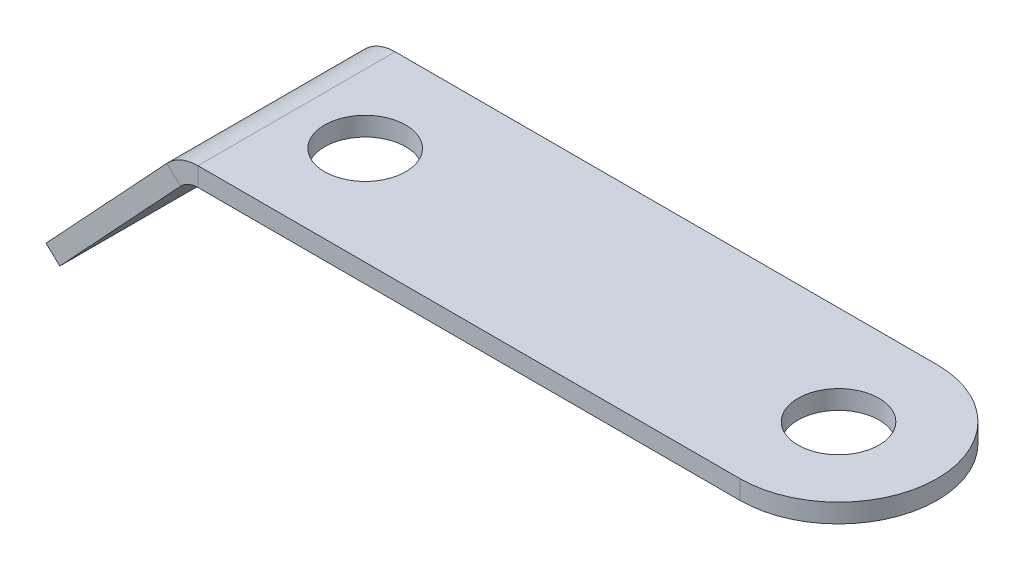
SolidWorks part; units mm, degrees
note: The reader was unsure of these and kept them because the rebuilt part matched: flange length of "Edge-Flange1".
ref_plane "Front Plane" through (0, 0, 0) normal (0, 0, 1) x (1, 0, 0)
ref_plane "Top Plane" through (0, 0, 0) normal (0, 1, 0) x (1, 0, 0)
ref_plane "Right Plane" through (0, 0, 0) normal (1, 0, 0) x (0, 0, -1)
sketch "Sketch1" plane through (0, 0, 0) normal (0, 1, 0) x (1, 0, 0)
  line L0 (44.45, 0) -> (44.45, 4.6736) construction
  line L1 (0, 0) -> (44.45, 0)
  line L2 (0, 0) -> (0, 15.875)
  line L3 (0, 15.875) -> (44.45, 15.875)
  line L4 (44.45, 11.2014) -> (44.45, 15.875) construction
  line L5 (44.45, 4.6736) -> (44.45, 11.2014) construction
  arc A0 (44.45, 15.875) -> (44.45, 0) centre (44.45, 7.9375) cw
  circle A1 centre (44.45, 7.9375) radius 3.2639
  circle A2 centre (6.35, 7.9375) radius 3.2639
  dimension "D3" = 6.5278
  dimension "D4" = 6.5278
  dimension "D1" = 15.875
  dimension "D2" = 44.45
  dimension "D5" = 38.1
base flange "Base-Flange1" sketch "Sketch1" thickness 1.5189 reverse thickness direction no parameters "D1"=1.905
edge flange "Edge-Flange1" sketch "Sketch8" flange angle 133 flange length 15.748 flange position material outside bend radius 1.905 thickness 1.5189 relief rectangular parameters "D6"=10
sketch "Sketch8" plane through (0, -1.5189, 0) normal (-0.7314, 0.682, 0) x (0, 0, -1)
  line L2 (0, 0) -> (0, 15.0876)
  line L3 (0, 15.0876) -> (15.875, 15.0876)
  line L4 (15.875, 15.0876) -> (15.875, 0)
  line L11 (15.875, 0) -> (0, 0) construction
  line L12 (15.875, 0) -> (0, 0)
bend "EdgeBend1" bend radius 1.905 bend angle 47 parameters "D5"=1
sketch "Bend-Lines1" [suppressed] plane through (0, 0, 0) normal (0, 1, 0) x (1, 0, 0)
sketch "Bounding-Box1" [suppressed] plane through (0, 0, 0) normal (0, 1, 0) x (1, 0, 0)
sheet metal parameters "Sheet-Metal1" thickness 1.5189 parameters "D1"=1.905
flat pattern "Flat-Pattern1" [suppressed]
sketch "Bend-Lines2" plane through (0, 0, 0) normal (0, 1, 0) x (1, 0, 0)
sketch3d "Bounding-Box2" [suppressed]
  line L0 (44.45, 7.9375, 0) -> (-7.9374, 7.9375, 0) construction
  line L1 (44.45, -7.9375, 0) -> (-7.9374, -7.9375, 0) construction
  line L2 (44.45, 7.9375, 0) -> (44.45, -7.9375, 0) construction
  line L3 (-7.9374, 7.9375, 0) -> (-7.9374, -7.9375, 0) construction
sheet metal parameters "Sheet-Metal2" thickness 1.5189 parameters "D1"=1.905
flat pattern "Flat-Pattern1"
sketch "Bend-Lines2" plane through (0, 0, 0) normal (0, 1, 0) x (1, 0, 0)
  line L0 (-0.2645, 15.875) -> (-0.2645, 0) construction
  line L1 (-0.2645, 15.875) -> (-0.2645, 0) construction
sketch3d "Bounding-Box2" [suppressed]
  line L0 (-60.0666, 7.9375, 0) -> (7.9374, 7.9375, 0) construction
  line L1 (-60.0666, -7.9375, 0) -> (7.9374, -7.9375, 0) construction
  line L2 (-60.0666, 7.9375, 0) -> (-60.0666, -7.9375, 0) construction
  line L3 (7.9374, 7.9375, 0) -> (7.9374, -7.9375, 0) construction
bend of the flat pattern "Flatten-<EdgeBend1>1"
